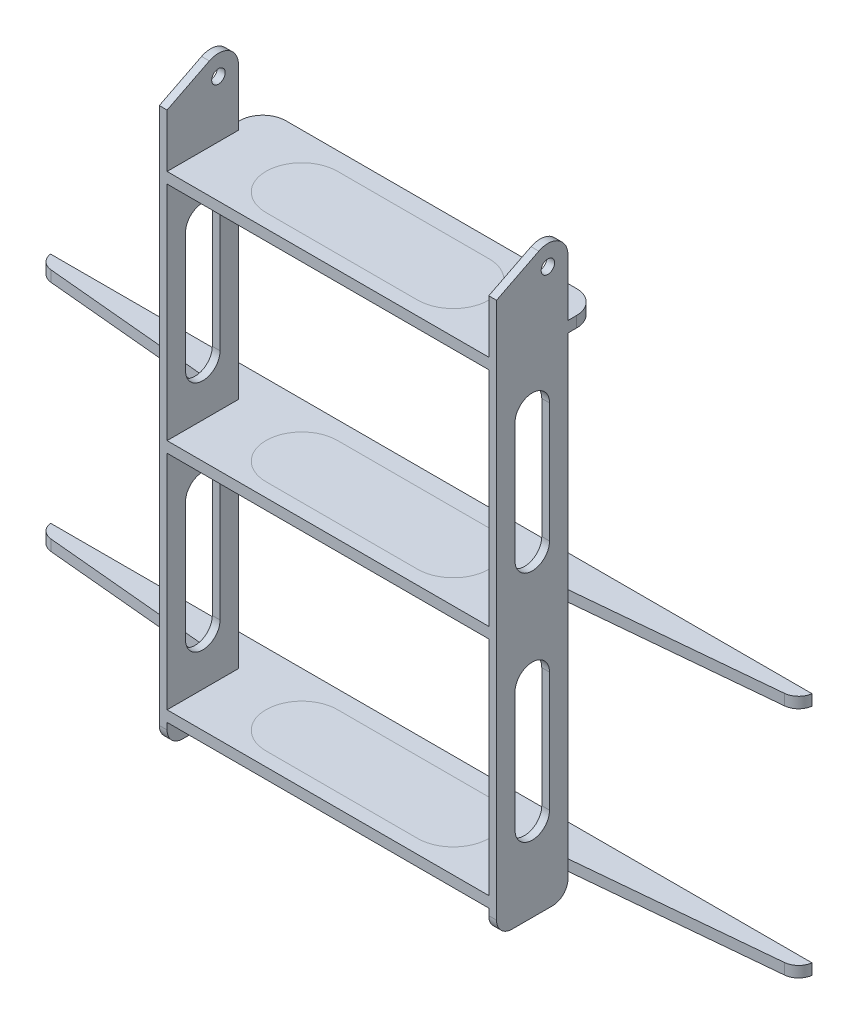
SolidWorks part; units mm, degrees
ref_plane "Front Plane" through (0, 0, 0) normal (0, 0, 1) x (1, 0, 0)
ref_plane "Top Plane" through (0, 0, 0) normal (0, 1, 0) x (1, 0, 0)
ref_plane "Right Plane" through (0, 0, 0) normal (1, 0, 0) x (0, 0, -1)
sketch "Sketch1" plane through (0, 0, 0) normal (0, 0, 1) x (1, 0, 0)
  line L1 (-618.735, -7) -> (618.735, -7)
  line L2 (-618.735, -7) -> (-618.735, 7)
  line L3 (-618.735, 7) -> (618.735, 7)
  line L4 (618.735, -7) -> (618.735, 7)
  line L5 (-618.735, -7) -> (618.735, 7) construction
  line L6 (-618.735, 7) -> (618.735, -7) construction
  point P0 (0, 0)
  dimension "D1" = 1237.47
  dimension "D2" = 14
extrude "Boss-Extrude1" add sketch "Sketch1" along normal blind 133
pattern_linear "LPattern3" count 3 spacing 300 along (0, -1, 0) of bodies 101
sketch "Sketch2" plane through (0, 7, 0) normal (0, 1, 0) x (1, 0, 0)
  line L0 (-618.735, 0) -> (-618.735, -133)
  line L1 (-618.735, -133) -> (-217.005, -133)
  line L2 (618.735, -133) -> (-618.735, -133) construction
  line L3 (-217.005, -133) -> (-217.005, -41.0624)
  line L6 (618.735, 0) -> (-618.735, 0) construction
  line L7 (-489.975, 0) -> (-618.735, 0)
  line L8 (-217.005, -41.0624) -> (-488.6398, -15.7679)
  line L9 (-488.6398, -15.7679) -> (-489.975, 0)
  line L10 (0, -73.15) -> (0, 73.15) construction
  line L11 (217.005, -41.0624) -> (488.6398, -15.7679)
  line L12 (217.005, -133) -> (217.005, -41.0624)
  line L13 (618.735, -133) -> (217.005, -133)
  line L14 (618.735, 0) -> (618.735, -133)
  line L15 (489.975, 0) -> (618.735, 0)
  line L16 (488.6398, -15.7679) -> (489.975, 0)
  dimension "D1" = 128.76
  dimension "D2" = 401.73
  dimension "D3" = 94.84
  dimension "D4" = 100.16
  dimension "D5" = 272.81
extrude "Cut-Extrude1" cut sketch "Sketch2" against normal through all
sketch "Sketch3" plane through (-217.005, 0, 0) normal (-1, 0, 0) x (0, 0, 1)
  line L0 (133, -293) -> (133, -307) construction
  line L1 (133, -635.5) -> (41.0624, -635.5)
  line L2 (133, -635.5) -> (133, 105.76)
  line L3 (133, 105.76) -> (41.0624, 105.76)
  line L4 (41.0624, -635.5) -> (41.0624, 105.76)
  line L5 (133, -635.5) -> (41.0624, 105.76) construction
  line L6 (133, 105.76) -> (41.0624, -635.5) construction
  line L7 (41.0624, -307) -> (41.0624, -293) construction
  line L8 (133, 7) -> (41.0624, 7) construction
  line L9 (133, -607) -> (41.0624, -607) construction
  point P0 (87.0312, -264.87)
  dimension "D1" = 98.76
  dimension "D2" = 28.5
extrude "Boss-Extrude2" add sketch "Sketch3" against normal blind 10
mirror "Mirror1" about plane through (0, 0, 0) normal (1, 0, 0) of "Boss-Extrude2"
sketch "Sketch4" plane through (0, 7, 0) normal (0, 1, 0) x (1, 0, 0)
  line L0 (-217.005, -133) -> (-217.005, -41.0624) construction
  line L1 (-521.6711, -222.7612) -> (-217.005, -222.7612)
  line L2 (-521.6711, -222.7612) -> (-521.6711, 40.6855)
  line L3 (-521.6711, 40.6855) -> (-217.005, 40.6855)
  line L4 (-217.005, -222.7612) -> (-217.005, 40.6855)
  line L5 (-521.6711, -222.7612) -> (-217.005, 40.6855) construction
  line L6 (-521.6711, 40.6855) -> (-217.005, -222.7612) construction
  line L7 (0, -73.15) -> (0, 73.15) construction
  line L8 (521.6711, 40.6855) -> (217.005, 40.6855)
  line L9 (217.005, -222.7612) -> (217.005, 40.6855)
  line L10 (521.6711, -222.7612) -> (217.005, -222.7612)
  line L11 (521.6711, -222.7612) -> (521.6711, 40.6855)
  point P0 (-369.3381, -91.0379)
extrude "Cut-Extrude2" cut sketch "Sketch4" against normal blind 86
sketch "Sketch5" plane through (-217.005, 0, 0) normal (-1, 0, 0) x (0, 0, 1)
  line L0 (133, 75.48) -> (78.5867, 102.9799)
  line L1 (133, 105.76) -> (133, -635.5) construction
  line L2 (41.0624, 105.76) -> (41.0624, 7) construction
  line L3 (133, 105.76) -> (41.0624, 105.76) construction
  line L4 (133, 75.48) -> (142.1387, 75.48)
  line L5 (142.1387, 75.48) -> (142.1387, 120.2923)
  line L6 (142.1387, 120.2923) -> (30.4421, 120.2923)
  line L7 (30.4421, 120.2923) -> (30.4421, 79.9)
  line L8 (30.4421, 79.9) -> (41.0624, 79.9)
  circle A0 centre (66.9224, 79.9) radius 8.65
  arc A1 (78.5867, 102.9799) -> (41.0624, 79.9) centre (66.9224, 79.9) ccw
  dimension "D1" = 17.3
  dimension "D2" = 25.86
  dimension "D3" = 25.86
  dimension "D4" = 4.42
extrude "Cut-Extrude3" cut sketch "Sketch5" against normal through all
fillet "Fillet1" radius 30 2 edges at (217.005, 0, 0) (-217.005, 0, 0)
fillet "Fillet2" radius 20 4 edges at (212.005, -635.5, 41.0624) (212.005, -635.5, 133) (-212.005, -635.5, 41.0624) (-212.005, -635.5, 133)
fillet "Fillet3" radius 20 4 edges at (488.6398, -300, 15.7679) (488.6398, -600, 15.7679) (-488.6398, -600, 15.7679) (-488.6398, -300, 15.7679)
sketch "Sketch6" plane through (-217.005, 0, 0) normal (-1, 0, 0) x (0, 0, 1)
  line L0 (87.0312, -73.05) -> (87.0312, -226.95) construction
  line L1 (109.2612, -73.05) -> (109.2612, -226.95)
  line L2 (64.8012, -73.05) -> (64.8012, -226.95)
  line L3 (41.0624, -300) -> (133, -300) construction
  line L4 (41.0624, -307) -> (41.0624, -293) construction
  line L5 (133, 75.48) -> (133, -615.5) construction
  line L6 (41.0624, 0) -> (133, 0) construction
  line L7 (87.0312, -526.95) -> (87.0312, -373.05) construction
  line L8 (109.2612, -526.95) -> (109.2612, -373.05)
  line L9 (64.8012, -526.95) -> (64.8012, -373.05)
  arc A0 (109.2612, -73.05) -> (64.8012, -73.05) centre (87.0312, -73.05) ccw
  arc A1 (64.8012, -226.95) -> (109.2612, -226.95) centre (87.0312, -226.95) ccw
  arc A2 (109.2612, -526.95) -> (64.8012, -526.95) centre (87.0312, -526.95) cw
  arc A3 (64.8012, -373.05) -> (109.2612, -373.05) centre (87.0312, -373.05) cw
  point P2 (87.0312, -150)
  point P16 (87.0312, 0)
  point P17 (87.0312, -300)
  point P20 (87.0312, -450)
  dimension "D2" = 22.23
  dimension "D1" = 153.9
  dimension "D3" = 73.05
extrude "Cut-Extrude4" cut sketch "Sketch6" against normal through all
sketch "Sketch7" plane through (0, 7, 0) normal (0, 1, 0) x (1, 0, 0)
  line L0 (-97.5, -69.14) -> (97.5, -69.14) construction
  line L1 (-97.5, -23.14) -> (97.5, -23.14)
  line L2 (-97.5, -115.14) -> (97.5, -115.14)
  arc A0 (-97.5, -23.14) -> (-97.5, -115.14) centre (-97.5, -69.14) ccw
  arc A1 (97.5, -115.14) -> (97.5, -23.14) centre (97.5, -69.14) ccw
  point P2 (0, -69.14)
  point P7 (0, 0)
  point P8 (0, -63.86)
  point P10 (0, -69.14)
  dimension "D2" = 46
  dimension "D1" = 195
split line "Split Line1"
